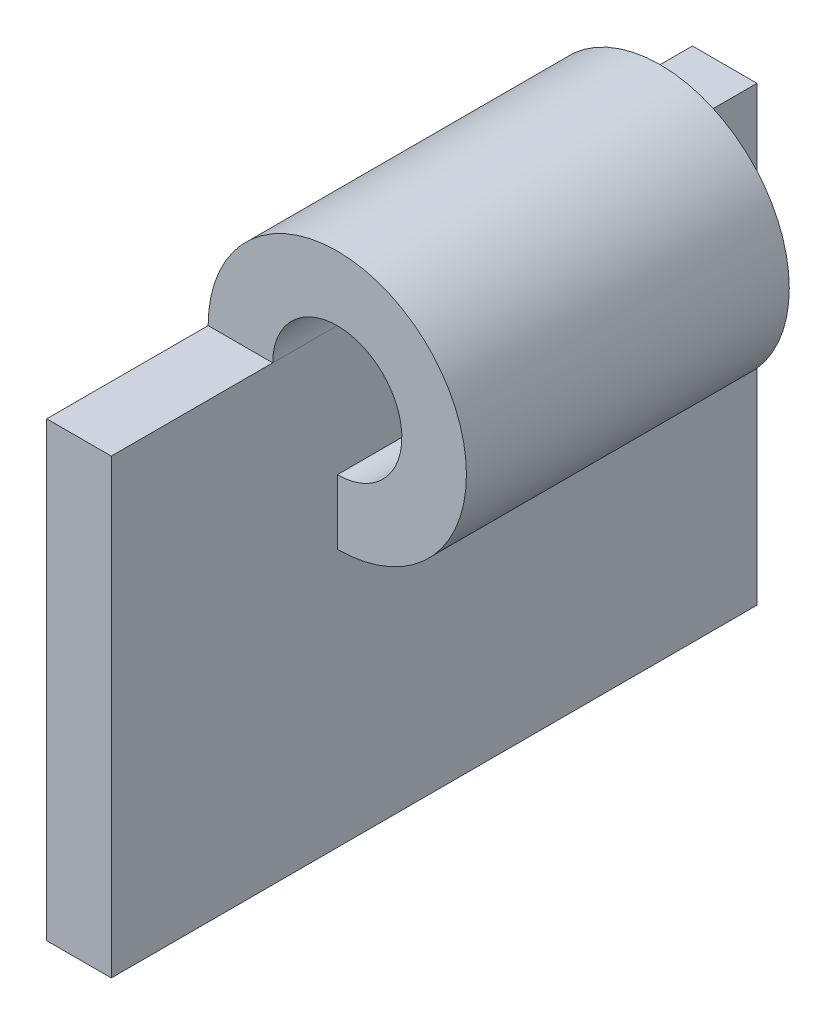
SolidWorks part; units mm, degrees
ref_plane "Front Plane" through (0, 0, 0) normal (0, 0, 1) x (1, 0, 0)
ref_plane "Top Plane" through (0, 0, 0) normal (0, 1, 0) x (1, 0, 0)
ref_plane "Right Plane" through (0, 0, 0) normal (1, 0, 0) x (0, 0, -1)
sketch "Sketch2" plane through (0, 0, 0) normal (0, 0, 1) x (1, 0, 0)
  line L0 (0, 0) -> (0, 14)
  line L1 (0, 14) -> (2, 14)
  line L2 (2, 14) -> (2, 0)
  line L3 (2, 0) -> (0, 0)
  line L4 (2, 14) -> (2, 10) construction
  line L5 (0, 14) -> (4, 14) construction
  line L6 (4, 18) -> (4, 10) construction
  line L7 (4, 14) -> (8, 14) construction
  line L8 (4, 12) -> (4, 10)
  arc A0 (2, 10.5359) -> (0, 14) centre (4, 14) ccw
  circle A1 centre (4, 14) radius 2
  dimension "D3" = 8
  dimension "D4" = 4
  dimension "D1" = 14
  dimension "D2" = 2
extrude "Boss-Extrude1" add sketch "Sketch2" along normal blind 20 contours L3 L2 L1 L0 region at (1, 7, 0)
ref_plane "Plane1" through (0, 0, 10) normal (0, 0, 1) x (1, 0, 0)
extrude "Boss-Extrude2" add sketch "Sketch2<8>" along normal blind 10 from offset 5 separate body contours A1 L8 A0 L1 region at (6.7484, 16.7484, 0)
sketch "Sketch2<8>" plane through (0, 0, 0) normal (0, 0, 1) x (1, 0, 0) same geometry as "Sketch2"
